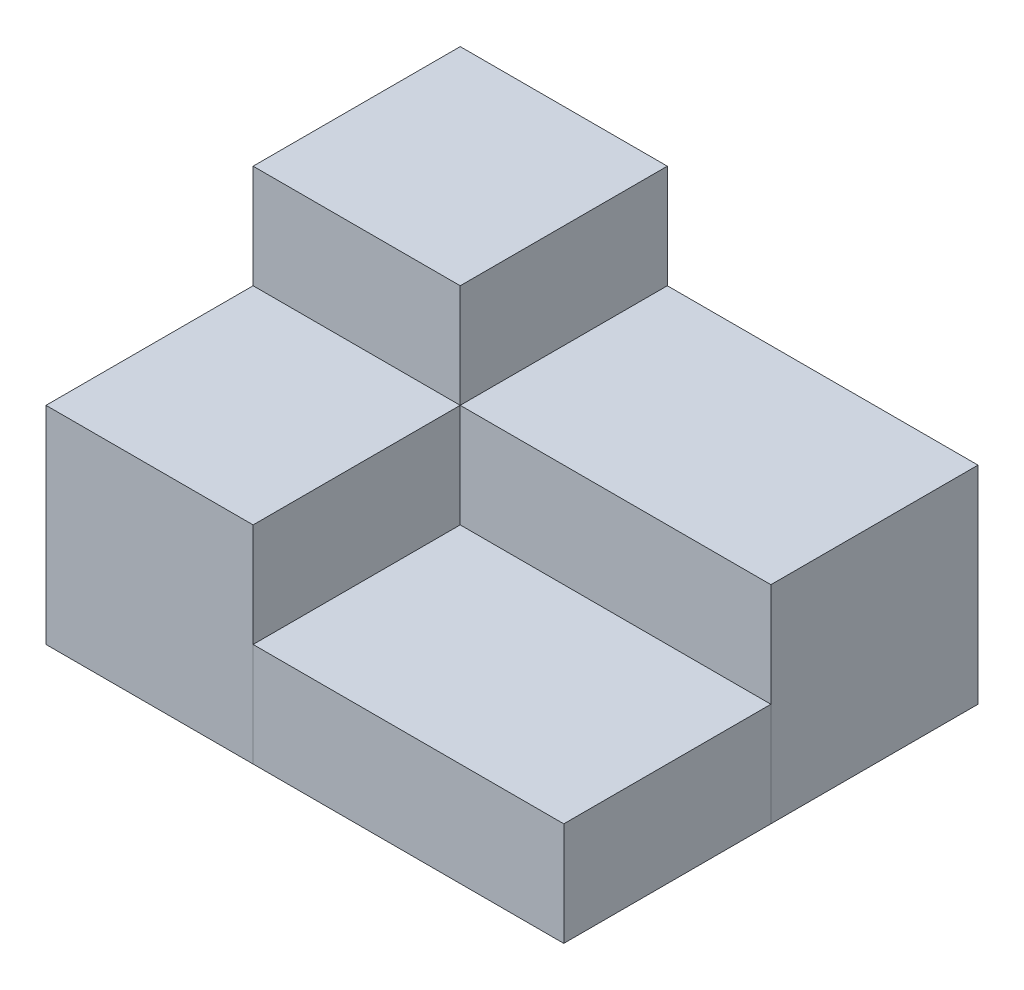
SolidWorks part; units mm, degrees
ref_plane "Front Plane" through (0, 0, 0) normal (0, 0, 1) x (1, 0, 0)
ref_plane "Top Plane" through (0, 0, 0) normal (0, 1, 0) x (1, 0, 0)
ref_plane "Right Plane" through (0, 0, 0) normal (1, 0, 0) x (0, 0, -1)
sketch "Sketch1" plane through (0, 0, 0) normal (0, 1, 0) x (1, 0, 0)
  line L0 (20, 40) -> (20, 0)
  line L1 (0, 0) -> (50, 0)
  line L2 (0, 0) -> (0, 40)
  line L3 (0, 40) -> (50, 40)
  line L4 (50, 0) -> (50, 40)
  line L5 (0, 20) -> (50, 20)
  dimension "D1" = 50
  dimension "D2" = 40
  dimension "D3" = 20
extrude "Boss-Extrude1" add sketch "Sketch1" along normal blind 20 contours L5 L2 L1 L0 | L0 L5 L4 L3 region at (35, 0, -30) region at (10, 0, -10)
extrude "Boss-Extrude3" add sketch "Sketch1<3>" along normal blind 10 separate body contours L5 L0 L1 L4 region at (35, 0, -10)
sketch "Sketch1<3>" plane through (0, 0, 0) normal (0, 1, 0) x (1, 0, 0) same geometry as "Sketch1"
extrude "Boss-Extrude4" add sketch "Sketch1<4>" along normal blind 30 separate body contours L2 L5 L0 L3 region at (10, 0, -30)
sketch "Sketch1<4>" plane through (0, 0, 0) normal (0, 1, 0) x (1, 0, 0) same geometry as "Sketch1"
